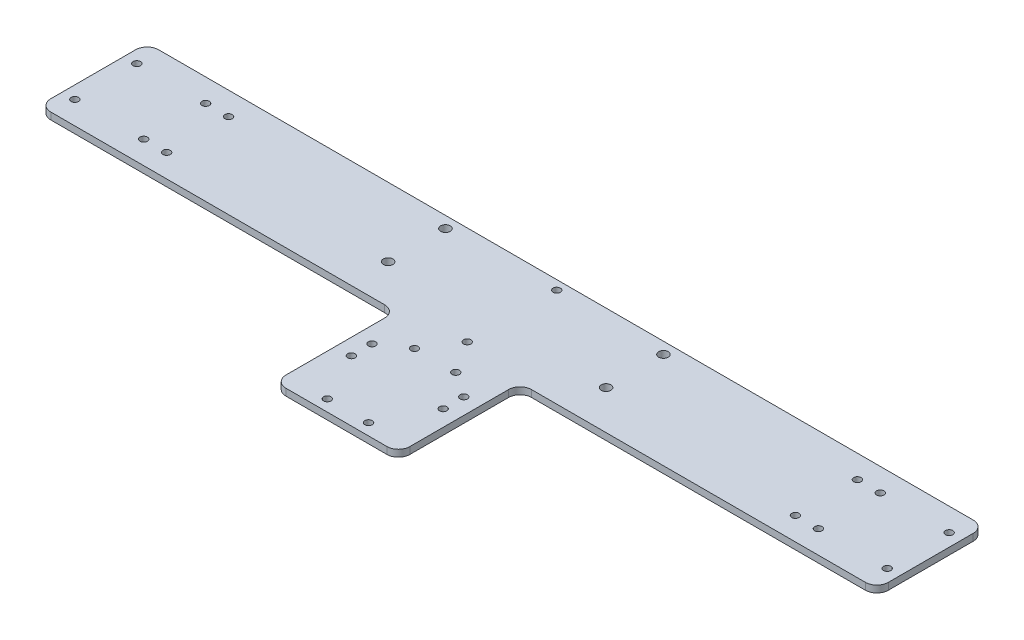
SolidWorks part; units mm, degrees
material "延性铁"
ref_plane "前视基准面" through (0, 0, 0) normal (0, 0, 1) x (1, 0, 0)
ref_plane "上视基准面" through (0, 0, 0) normal (0, 1, 0) x (1, 0, 0)
ref_plane "右视基准面" through (0, 0, 0) normal (1, 0, 0) x (0, 0, -1)
ref_plane "基准面4" through (0, 0, 0) normal (0, -1, 0) x (1, 0, 0)
sketch "草图1" plane through (0, 0, 0) normal (0, -1, 0) x (1, 0, 0)
  line L0 (-27, 0) -> (27, 0)
  line L1 (-182.5, -100) -> (182.5, -100)
  line L2 (173.8772, -76.5) -> (143.8772, -76.5) construction
  line L3 (-182.5, -53) -> (-27, -53)
  line L4 (-182.5, -53) -> (-182.5, -100)
  line L5 (27, 0) -> (27, -53)
  line L6 (182.5, -53) -> (182.5, -100)
  line L7 (182.5, -53) -> (27, -53)
  line L8 (-173.8772, -76.5) -> (-143.8772, -76.5) construction
  line L9 (0, -197.5655) -> (0, 22.9702) construction
  line L10 (-27, 0) -> (-27, -53)
  line L12 (0, 44.5655) -> (0, -175.9702) construction
  circle A0 centre (177, -63) radius 1.6
  circle A1 centre (-177, -90) radius 1.6
  circle A2 centre (-9, -43) radius 1.6
  circle A3 centre (-9, -5) radius 1.6
  circle A4 centre (-20, -35.5) radius 1.6
  circle A5 centre (-20, -26.5) radius 1.6
  circle A6 centre (-47.5, -95) radius 2.1
  circle A7 centre (-47.5, -70) radius 2.1
  circle A8 centre (-137, -63) radius 1.6
  circle A9 centre (-137, -90) radius 1.6
  circle A10 centre (-177, -63) radius 1.6
  circle A11 centre (137, -90) radius 1.6
  circle A12 centre (137, -63) radius 1.6
  circle A13 centre (47.5, -70) radius 2.1
  circle A14 centre (47.5, -95) radius 2.1
  circle A15 centre (20, -26.5) radius 1.6
  circle A16 centre (20, -35.5) radius 1.6
  circle A17 centre (9, -5) radius 1.6
  circle A18 centre (9, -43) radius 1.6
  circle A19 centre (177, -90) radius 1.6
  circle A20 centre (0, -57) radius 1.6
  circle A21 centre (0, -96) radius 1.6
  circle A22 centre (-147, -63) radius 1.6
  circle A23 centre (-147, -90) radius 1.6
  circle A24 centre (147, -63) radius 1.6
  circle A25 centre (147, -90) radius 1.6
  point P25 (0, 0)
  point P54 (0, -100)
  dimension "D3" = 10
  dimension "D6" = 38
  dimension "D14" = 5
  dimension "D15" = 7
  dimension "D16" = 30.5
  dimension "D17" = 9
  dimension "D22" = 4
  dimension "D23" = 13.5
  dimension "D10" = 177
  dimension "D11" = 40
  dimension "D12" = 9
  dimension "D4" = 9
  dimension "D5" = 47
  dimension "D7" = 25
  dimension "D8" = 10
  dimension "D20" = 5.5
  dimension "D24" = 30
  dimension "D27" = 10
  dimension "D13" = 47.5
  dimension "D28" = 7
  dimension "D9" = 47.5
  dimension "D25" = 10
  dimension "D18" = 5
  dimension "D21" = 11
extrude "凸台-拉伸1" add sketch "草图1" against normal blind 3
fillet "圆角1" radius 5 8 edges at (-182.5, 1.5, -100) (-182.5, 1.5, -53) (182.5, 1.5, -100) (182.5, 1.5, -53) (27, 1.5, -53) (27, 1.5, 0) (-27, 1.5, 0) (-27, 1.5, -53) first distance on face at (0, 1.5, -100) first distance on face at (-104.75, 1.5, -53) first distance on face at (104.75, 1.5, -53) first distance on face at (0, 1.5, 0)
